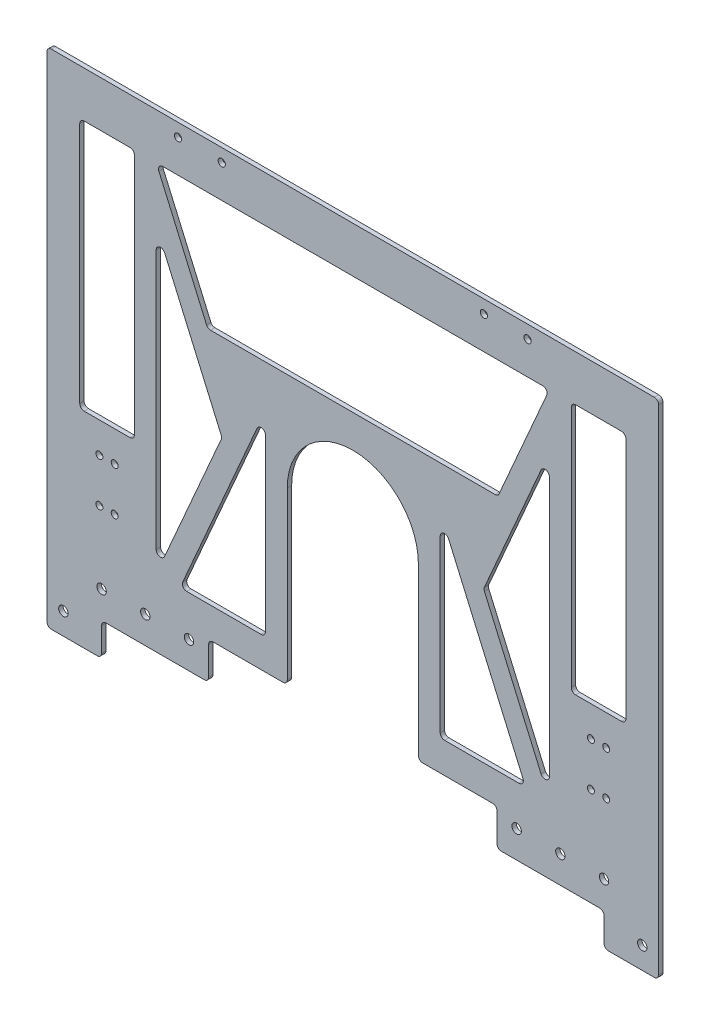
SolidWorks part; units mm, degrees
material "环氧板"
ref_plane "前视基准面" through (0, 0, 0) normal (0, 0, 1) x (1, 0, 0)
ref_plane "上视基准面" through (0, 0, 0) normal (0, 1, 0) x (1, 0, 0)
ref_plane "右视基准面" through (0, 0, 0) normal (1, 0, 0) x (0, 0, -1)
other "Configuration Table"
sketch "草图1" plane through (0, 0, 0) normal (0, 0, 1) x (1, 0, 0)
  line L1 (-140, 115) -> (140, 115)
  line L2 (-140, 115) -> (-140, -115)
  line L3 (-140, -115) -> (140, -115)
  line L4 (140, 115) -> (140, -115)
  line L5 (-140, 115) -> (140, -115) construction
  line L6 (-140, -115) -> (140, 115) construction
  point P0 (0, 0)
  dimension "D1" = 280
  dimension "D2" = 230
extrude "凸台-拉伸1" add sketch "草图1" along normal blind 2
sketch "草图2" plane through (0, 0, 2) normal (0, 0, 1) x (1, 0, 0)
  line L0 (-140, -115) -> (140, -115) construction
  line L1 (-140, 115) -> (-140, -115) construction
  line L2 (0, 0) -> (0, -147.9054) construction
  line L3 (-115, -87.5) -> (-95, -87.5) construction
  circle A0 centre (-132.5, -105) radius 2.15
  circle A1 centre (132.5, -105) radius 2.15
  circle A2 centre (-115, -87.5) radius 2.15
  circle A3 centre (-95, -87.5) radius 2.15
  circle A4 centre (-75, -87.5) radius 2.15
  circle A5 centre (75, -87.5) radius 2.15
  circle A6 centre (95, -87.5) radius 2.15
  circle A7 centre (115, -87.5) radius 2.15
  dimension "D1" = 10
  dimension "D2" = 7.5
  dimension "D3" = 4.3
  dimension "D4" = 17.5
  dimension "D5" = 3
  dimension "17.5" = 17.5
  dimension "D6" = 20
extrude "切除-拉伸1" cut sketch "草图2" against normal through all
sketch "草图3" plane through (0, 0, 2) normal (0, 0, 1) x (1, 0, 0)
  line L0 (-140, -115) -> (140, -115) construction
  line L1 (-30, -5) -> (-30, -115)
  line L2 (30, -5) -> (30, -115)
  line L3 (30, -115) -> (-30, -115)
  circle A0 centre (0, -5) radius 30
  line M12 (-140, -115) -> (140, -115)
  dimension "D1" = 110
  dimension "D2" = 60
extrude "切除-拉伸2" cut sketch "草图3" against normal through all contours A0 | A0 L1 L2 M12 region at (0, -71.5216, 2) region at (0, -5, 2)
sketch "草图4" plane through (0, 0, 2) normal (0, 0, 1) x (1, 0, 0)
  line L0 (-140, 115) -> (-140, -115) construction
  line L1 (-140, -115) -> (-30, -115) construction
  line L2 (-109, -35) -> (-116, -35) construction
  line L3 (0, 0) -> (0, -99.1483) construction
  circle A0 centre (-109, -35) radius 1.6
  circle A1 centre (-109, -55) radius 1.6
  circle A2 centre (-116, -35) radius 1.6
  circle A3 centre (-116, -55) radius 1.6
  circle A4 centre (116, -55) radius 1.6
  circle A5 centre (116, -35) radius 1.6
  circle A6 centre (109, -55) radius 1.6
  circle A7 centre (109, -35) radius 1.6
  dimension "D1" = 3.2
  dimension "D2" = 20
  dimension "D4" = 60
  dimension "D3" = 31
  dimension "D6" = 7
  dimension "D5" = 2
extrude "切除-拉伸3" cut sketch "草图4" against normal through all
sketch "草图5" plane through (0, 0, 2) normal (0, 0, 1) x (1, 0, 0)
  line L0 (140, 115) -> (-140, 115) construction
  line L1 (-140, 115) -> (-140, -115) construction
  line L2 (0, 0) -> (0, 162.8227) construction
  line L3 (140, -115) -> (140, 115) construction
  line L4 (30, -115) -> (140, -115) construction
  line L5 (-140, -115) -> (-30, -115) construction
  circle A0 centre (-60, 109) radius 1.65
  circle A1 centre (-80, 109) radius 1.65
  circle A2 centre (80, 109) radius 1.65
  circle A3 centre (60, 109) radius 1.65
  dimension "D1" = 6
  dimension "D2" = 3.3
  dimension "D3" = 20
  dimension "D4" = 60
extrude "切除-拉伸4" cut sketch "草图5" against normal through all
sketch "草图6" plane through (0, 0, 2) normal (0, 0, 1) x (1, 0, 0)
  circle A0 centre (0, 0) radius 104 construction
  dimension "D1" = 208
sketch "草图7" plane through (0, 0, 2) normal (0, 0, 1) x (1, 0, 0)
  line L0 (-90, 69) -> (-90, -69)
  line L1 (-90, -69) -> (-59.8859, 0)
  line L2 (-59.8859, 0) -> (-90, 69)
  line L3 (0, 0) -> (0, -89.6558) construction
  line L4 (-90, 94) -> (-66.4325, 40)
  line L7 (66.4325, 40) -> (90, 94)
  line L8 (90, 94) -> (-90, 94)
  line L9 (-66.4325, 40) -> (66.4325, 40)
  line L10 (-140, 115) -> (-140, -115) construction
  line L11 (-40, 20.5644) -> (-79.0891, -69)
  line L12 (-79.0891, -69) -> (-40, -69)
  line L13 (-40, -69) -> (-40, 20.5644)
  line L14 (-30, -5) -> (-30, -115) construction
  line L15 (40, -69) -> (40, 20.5644)
  line L16 (79.0891, -69) -> (40, -69)
  line L17 (40, 20.5644) -> (79.0891, -69)
  line L18 (59.8859, 0) -> (90, 69)
  line L19 (90, -69) -> (59.8859, 0)
  line L20 (90, 69) -> (90, -69)
  line L21 (100, 94) -> (100, -21)
  line L22 (-125, 94) -> (-100, 94)
  line L23 (-125, 94) -> (-125, -21)
  line L24 (-125, -21) -> (-100, -21)
  line L25 (-100, 94) -> (-100, -21)
  line L26 (125, -21) -> (100, -21)
  line L27 (125, 94) -> (125, -21)
  line L28 (125, 94) -> (100, 94)
  line L29 (115, -115) -> (115, -100)
  line L30 (-30, -115) -> (-115, -115)
  line L31 (-30, -115) -> (-30, -100)
  line L32 (-30, -100) -> (-115, -100)
  line L33 (-115, -115) -> (-115, -100)
  line L34 (30, -100) -> (115, -100)
  line L35 (30, -115) -> (30, -100)
  line L36 (30, -115) -> (115, -115)
  circle A0 centre (60, 109) radius 1.65 construction
  dimension "D1" = 15
  dimension "D2" = 10
  dimension "D3" = 25
  dimension "D4" = 40
  dimension "D5" = 50
  dimension "D6" = 10
  dimension "D7" = 10
  dimension "D8" = 10
  dimension "D9" = 15
  dimension "D10" = 115
  dimension "D11" = 85
  dimension "D12" = 15
extrude "切除-拉伸5" cut sketch "草图7" against normal through all
sketch "草图9" plane through (0, 0, 2) normal (0, 0, 1) x (1, 0, 0)
  line L0 (0, 0) -> (0, -134.4577) construction
  line L1 (66, -100) -> (66, -83)
  line L2 (-30, -100) -> (-66, -100)
  line L3 (-30, -100) -> (-30, -83)
  line L4 (-30, -83) -> (-66, -83)
  line L5 (-66, -100) -> (-66, -83)
  line L6 (30, -83) -> (66, -83)
  line L7 (30, -100) -> (30, -83)
  line L8 (30, -100) -> (66, -100)
  dimension "D1" = 17
  dimension "D2" = 36
extrude "切除-拉伸6" cut sketch "草图9" against normal through all
fillet "圆角1" radius 2 24 edges at (-90, -69, 1) (125, -21, 1) (100, -21, 1) (100, 94, 1) (125, 94, 1) (90, 69, 1) (90, -69, 1) (59.8859, 0, 1) (-100, 94, 1) (-100, -21, 1) (-125, -21, 1) (-125, 94, 1) (-90, 94, 1) (90, 94, 1) (66.4325, 40, 1) (-66.4325, 40, 1) (-40, 20.5644, 1) (-40, -69, 1) (-79.0891, -69, 1) (40, 20.5644, 1) (79.0891, -69, 1) (40, -69, 1) (-90, 69, 1) (-59.8859, 0, 1)
fillet "圆角2" radius 2 14 edges at (-115, -100, 1) (-115, -115, 1) (-140, -115, 1) (140, 115, 1) (140, -115, 1) (115, -115, 1) (115, -100, 1) (-140, 115, 1) (66, -100, 1) (66, -83, 1) (30, -83, 1) (-66, -100, 1) (-30, -83, 1) (-66, -83, 1)
